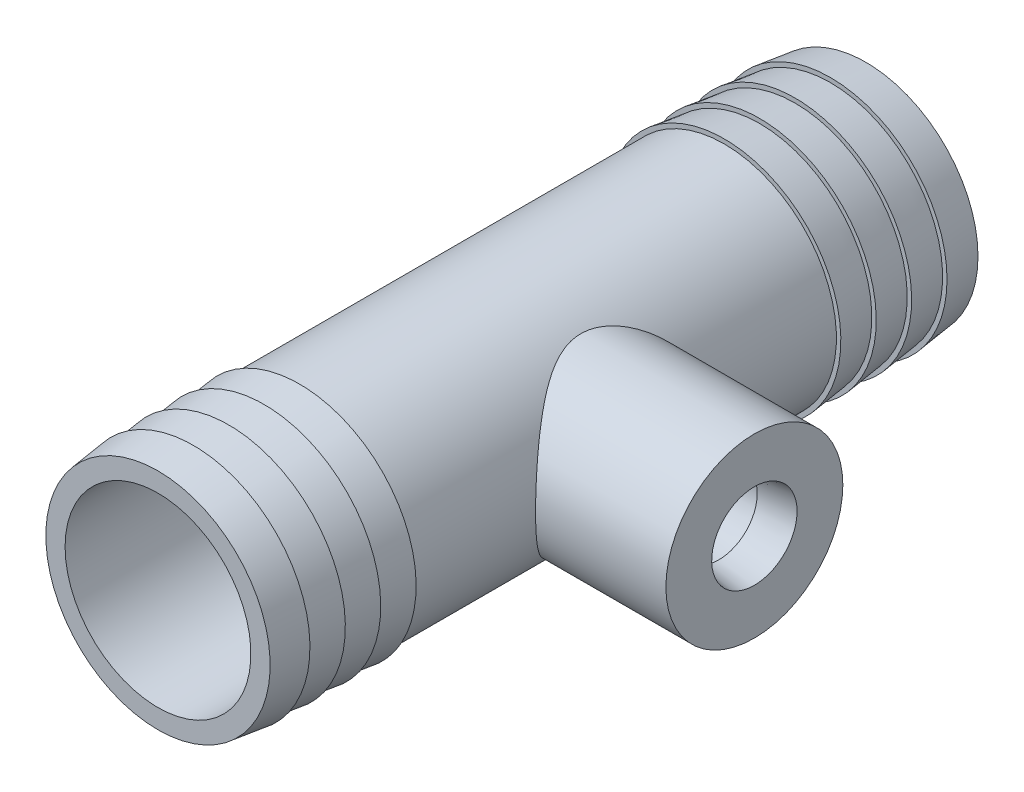
SolidWorks part; units mm, degrees
ref_plane "Front Plane" through (0, 0, 0) normal (0, 0, 1) x (1, 0, 0)
ref_plane "Top Plane" through (0, 0, 0) normal (0, 1, 0) x (1, 0, 0)
ref_plane "Right Plane" through (0, 0, 0) normal (1, 0, 0) x (0, 0, -1)
sketch "Sketch1" plane through (0, 0, 0) normal (1, 0, 0) x (0, 0, -1)
  circle A0 centre (0, 0) radius 10
  dimension "D1" = 20
extrude "Boss-Extrude1" add sketch "Sketch1" along normal blind 10 and the other way blind 10
sketch "Sketch2" plane through (10, 0, 0) normal (1, 0, 0) x (0, 0, -1)
  circle A0 centre (0, 0) radius 4.825
  dimension "D1" = 9.65
sketch "Sketch3" plane through (10, 0, 0) normal (1, 0, 0) x (0, 0, -1)
  circle A0 centre (0, 0) radius 9.525
sketch "Sketch11" plane through (0, 0, 0) normal (0, 0, 1) x (1, 0, 0)
  circle A0 centre (-17.4005, 0) radius 12.675
  point P2 (-20.2876, -0.404)
  point P3 (-17.4005, 0)
  dimension "D1" = 25.35
extrude "Boss-Extrude2" add sketch "Sketch11" along normal blind 40 and the other way blind 40 contours A0
sketch "Sketch12" plane through (0, 0, -40) normal (0, 0, -1) x (-1, 0, 0)
  circle A0 centre (17.4005, 0) radius 10.5
  dimension "D1" = 21
extrude "Cut-Extrude6" cut sketch "Sketch12" against normal through all
extrude "Cut-Extrude7" cut sketch "Sketch2" against normal blind 30
sketch "Sketch13" plane through (0, 0, 0) normal (0, 0, 1) x (1, 0, 0)
  line L0 (10, 4.825) -> (6, 4.825)
  line L1 (10, -9.525) -> (10, 9.525) construction
  line L2 (10, 4.825) -> (-8.0747, 4.825) construction
  line L3 (6, 4.825) -> (6, 4.325)
  line L4 (6, 4.325) -> (10, 4.825)
  dimension "D1" = 4
  dimension "D2" = 0.5
sketch "Sketch14" plane through (0, 0, 0) normal (0, 0, 1) x (1, 0, 0)
  line L0 (10, 0) -> (-1.8428, 0)
  line L1 (10, -9.525) -> (10, 9.525) construction
revolve "Revolve1" add sketch "Sketch13" angle 360 about L0
pattern_linear "LPattern1" count 4 spacing 4 along (-1, 0, 0) of "Revolve1"
sketch "Sketch15" plane through (0, 0, -40) normal (0, 0, -1) x (-1, 0, 0)
  line L0 (17.4005, -12.675) -> (17.4005, 12.675)
  circle A0 centre (17.4005, 0) radius 12.675 construction
sketch "Sketch16" plane through (0, 0, 40) normal (0, 0, 1) x (1, 0, 0)
  line L0 (-17.4005, 12.675) -> (-17.4005, -12.675)
ref_plane "Plane1" through (-17.4005, 0, 0) normal (1, 0, 0) x (0, 0, -1)
sketch "Sketch17" plane through (-17.4005, 0, 0) normal (1, 0, 0) x (0, 0, -1)
  line L0 (-40, 12.675) -> (-36, 12.675)
  line L1 (40, 12.675) -> (-40, 12.675) construction
  line L2 (-36, 12.675) -> (-36, 13.175)
  line L3 (-36, 13.175) -> (-40, 12.675)
  dimension "D1" = 4
  dimension "D2" = 0.5
sketch "Sketch18" plane through (-17.4005, 0, 0) normal (1, 0, 0) x (0, 0, -1)
  line L0 (-40, 0) -> (40, 0)
  line L1 (-40, 12.675) -> (-40, -12.675) construction
  line L2 (40, -12.675) -> (40, 12.675) construction
revolve "Revolve2" add sketch "Sketch17" angle 360 about L0
pattern_linear "LPattern2" count 4 spacing 4 along (0, 0, -1) of "Revolve2"
mirror "Mirror1" about plane through (0, 0, 0) normal (0, 0, 1) of "LPattern2"
